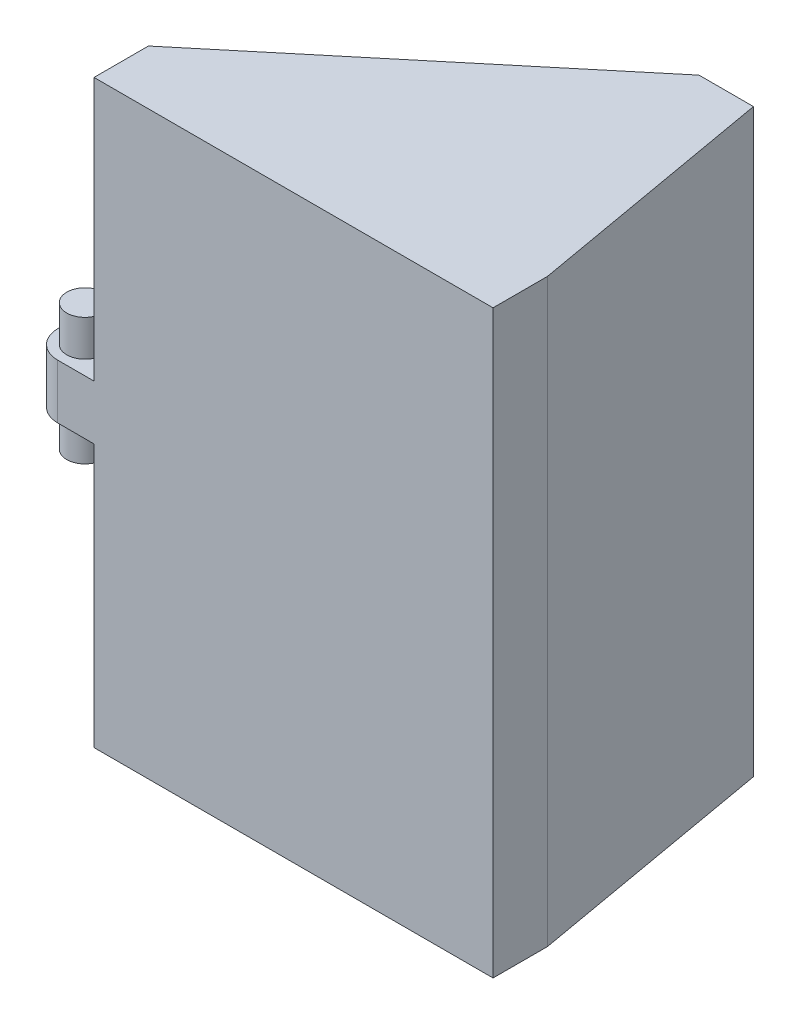
SolidWorks part; units mm, degrees
ref_plane "前视基准面" through (0, 0, 0) normal (0, 0, 1) x (1, 0, 0)
ref_plane "上视基准面" through (0, 0, 0) normal (0, 1, 0) x (1, 0, 0)
ref_plane "右视基准面" through (0, 0, 0) normal (1, 0, 0) x (0, 0, -1)
sketch "草图1" plane through (0, 0, 0) normal (0, 1, 0) x (1, 0, 0)
  line L0 (0, 0) -> (120, 0)
  line L1 (0, 15) -> (120, 15)
  line L7 (120, 15) -> (120, 0)
  arc A1 (0, 0) -> (0, 15) centre (0, 7.5) cw
  circle A3 centre (0, 7.5) radius 5
extrude "凸台-拉伸1" add sketch "草图1" along normal blind 7.5 and the other way blind 7.5
ref_plane "基准面4" through (0, 17.5, 0) normal (0, 1, 0) x (1, 0, 0)
sketch "草图2" plane through (0, 0, 0) normal (0, 1, 0) x (1, 0, 0)
  circle A0 centre (0, 7.5) radius 5
extrude "凸台-拉伸2" add sketch "草图2" against normal mid plane 35
sketch "草图3" plane through (0, 0, 0) normal (0, 1, 0) x (1, 0, 0)
  line L1 (10, 0) -> (120, 0)
  line L2 (10, 0) -> (10, 15)
  line L3 (10, 15) -> (120, 15)
  line L4 (120, 0) -> (120, 15)
extrude "凸台-拉伸3" add sketch "草图3" along normal mid plane 160
sketch "草图4" plane through (0, 80, 0) normal (0, 1, 0) x (1, 0, 0)
  line L0 (120, 15) -> (105, 15)
  line L1 (120, 15) -> (10, 15) construction
  line L2 (105, 15) -> (92.8446, 83.9365)
  line L3 (92.8446, 83.9365) -> (107.8446, 83.9365)
  line L4 (107.8446, 83.9365) -> (120, 15)
extrude "凸台-拉伸4" add sketch "草图4" against normal up to surface (160 mm away) up to face at (65, -80, -7.5)
sketch "草图5" plane through (0, 80, 0) normal (0, 1, 0) x (1, 0, 0)
  line L0 (10, 15) -> (92.8446, 83.9365)
  line L1 (92.8446, 83.9365) -> (105, 15)
  line L2 (105, 15) -> (10, 15)
  point P6 (105, 65)
  point P7 (103.8176, 64.2404)
  point P8 (96.3176, 64.2404)
extrude "凸台-拉伸5" add sketch "草图5" against normal blind 5
sketch "草图6" plane through (0, -80, 0) normal (0, -1, 0) x (1, 0, 0)
  line L0 (10, -15) -> (92.8446, -83.9365)
  line L2 (105, -15) -> (10, -15) construction
  line L3 (92.8446, -83.9365) -> (105, -15) construction
  line L4 (105, -15) -> (10, -15)
  line L5 (92.8446, -83.9365) -> (105, -15)
extrude "凸台-拉伸6" add sketch "草图6" against normal blind 5
chamfer "倒角1" distance 15 angle 85 1 edges at (92.8446, 0, -83.9365) first distance on face at (97.8446, 0, -83.9365)
fillet "圆角1" radius 10 1 edges at (105, 0, -15)
